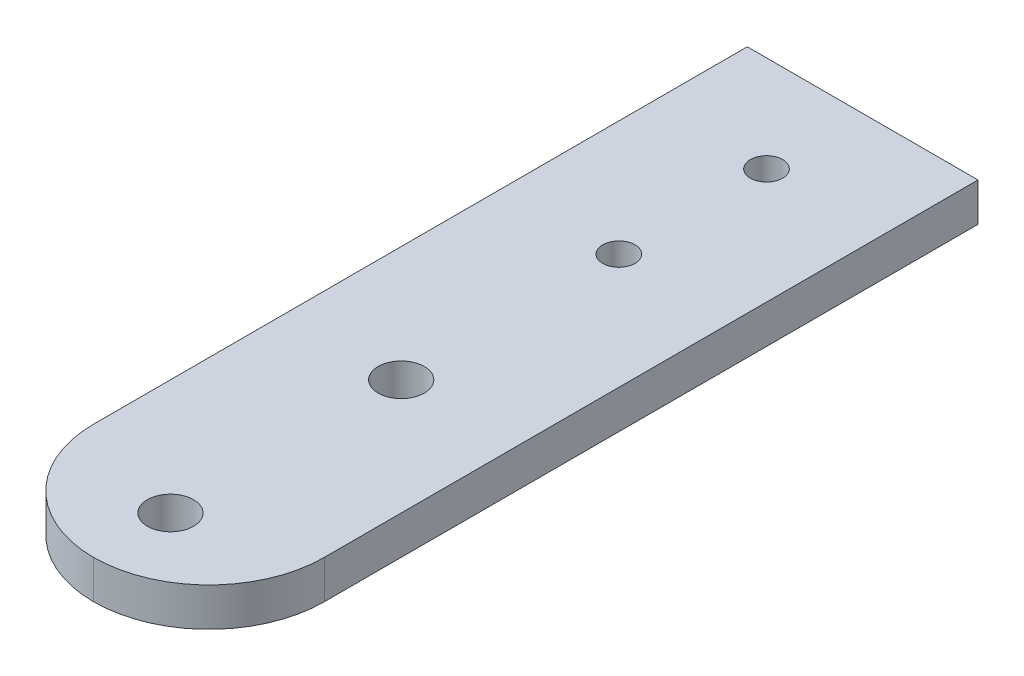
SolidWorks part; units mm, degrees
ref_plane "Plan de face" through (0, 0, 0) normal (0, 0, 1) x (1, 0, 0)
ref_plane "Plan de dessus" through (0, 0, 0) normal (0, 1, 0) x (1, 0, 0)
ref_plane "Plan de droite" through (0, 0, 0) normal (1, 0, 0) x (0, 0, -1)
sketch "Esquisse1" plane through (0, 0, 0) normal (0, 0, 1) x (1, 0, 0)
  line L1 (-7.5, -1.25) -> (7.5, -1.25)
  line L2 (-7.5, -1.25) -> (-7.5, 1.25)
  line L3 (-7.5, 1.25) -> (7.5, 1.25)
  line L4 (7.5, -1.25) -> (7.5, 1.25)
  line L5 (-7.5, -1.25) -> (7.5, 1.25) construction
  line L6 (-7.5, 1.25) -> (7.5, -1.25) construction
  point P0 (0, 0)
  dimension "D1" = 2.5
  dimension "D2" = 15
extrude "Extrusion1" add sketch "Esquisse1" along normal blind 50
sketch "Esquisse2" plane through (0, 1.25, 0) normal (0, 1, 0) x (1, 0, 0)
  line L0 (7.5, -50) -> (-7.5, -50) construction
  circle A0 centre (0, -45) radius 1.5
  dimension "D1" = 3
  dimension "D2" = 5
extrude "Extrusion2" cut sketch "Esquisse2" against normal through all
pattern_linear "Répétition linéaire1" count 2 spacing 15 along (0, 0, -1) of "Extrusion2"
fillet "Congé1" radius 7.5 2 edges at (-7.5, 0, 50) (7.5, 0, 50)
sketch "Esquisse5" plane through (0, 1.25, 0) normal (0, 1, 0) x (-1, 0, 0)
  circle A0 centre (0, 6.2496) radius 1.05
  dimension "D1" = 2.1
extrude "Enlèv. mat.-Extru.3" cut sketch "Esquisse5" against normal blind 10
sketch "Esquisse6" plane through (0, 1.25, 0) normal (0, 1, 0) x (1, 0, 0)
  circle A0 centre (0, -15.8496) radius 1.05
  dimension "D1" = 2.1
extrude "Enlèv. mat.-Extru.4" cut sketch "Esquisse6" against normal blind 10
